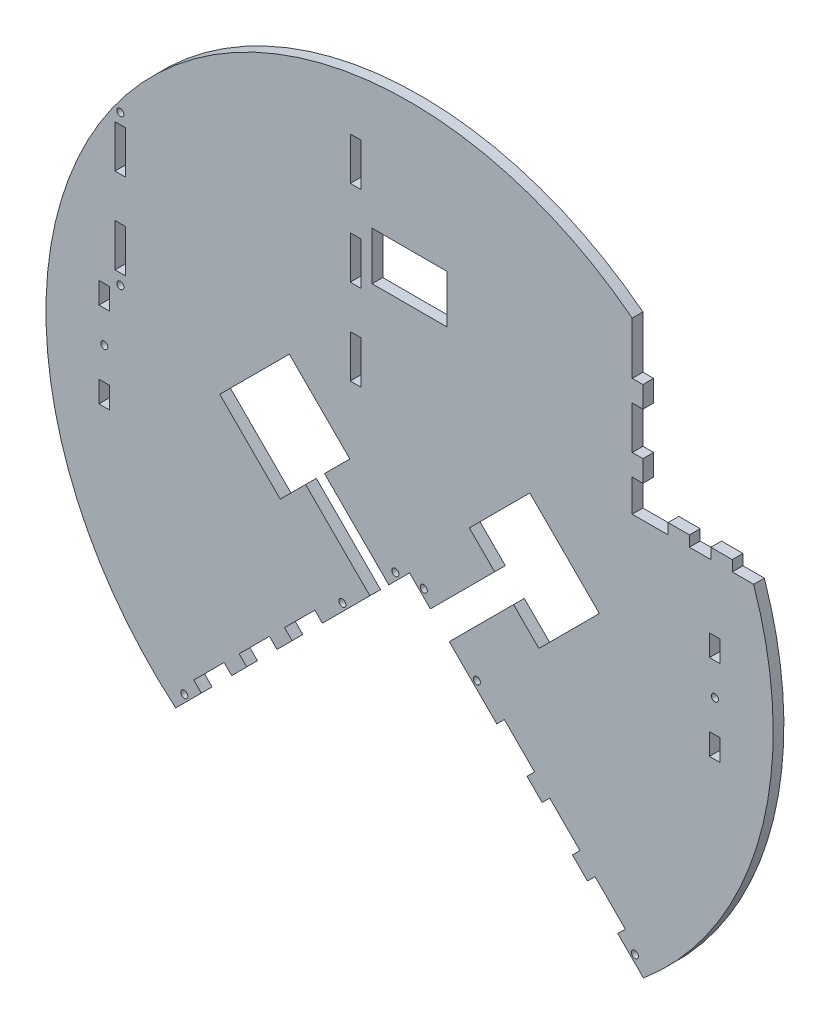
SolidWorks part; units mm, degrees
ref_plane "Front Plane" through (0, 0, 0) normal (0, 0, 1) x (1, 0, 0)
ref_plane "Top Plane" through (0, 0, 0) normal (0, 1, 0) x (1, 0, 0)
ref_plane "Right Plane" through (0, 0, 0) normal (1, 0, 0) x (0, 0, -1)
sketch "Sketch1" plane through (0, 0, 0) normal (0, 0, 1) x (1, 0, 0)
  circle A0 centre (0, 0) radius 215.9
  arc A1 (209.8384, 50.8) -> (202.0059, 76.2) centre (0, 0) ccw construction
extrude "Boss-Extrude1" add sketch "Sketch1" along normal blind 6.35 contours A0
sketch "Sketch2" plane through (0, 0, 0) normal (0, 0, -1) x (-1, 0, 0)
  line L0 (0, -26.4411) -> (138.8703, -165.3114)
  line L2 (0, -26.4411) -> (-138.8703, -165.3114)
  line L3 (-139.4438, -165.8849) -> (0, -26.4411) construction
  line L4 (0, 0) -> (0, -240.5018) construction
  arc A4 (-138.8703, -165.3114) -> (138.8703, -165.3114) centre (0, 0) ccw
  circle A5 centre (0, 0) radius 215.9 construction
  dimension "D1" = 90
extrude "Cut-Extrude1" cut sketch "Sketch2" against normal through all
sketch "Sketch3" plane through (0, 0, 6.35) normal (0, 0, 1) x (1, 0, 0)
  line L0 (71.393, 50.3401) -> (112.7022, 9.0309)
  line L1 (71.393, 50.3401) -> (35.472, 14.4191)
  line L2 (112.7022, 9.0309) -> (76.7812, -26.8901)
  line L3 (35.472, 14.4191) -> (76.7812, -26.8901)
  line L4 (76.7812, -26.8901) -> (72.2911, -22.4) construction
  line L5 (97.2507, 34.8885) -> (46.1575, -16.2046) construction
  line L6 (50.5139, -0.6229) -> (61.7393, -11.8482)
  line L7 (50.5139, -0.6229) -> (12.3479, -38.7889)
  line L8 (61.7393, -11.8482) -> (23.5732, -50.0143)
  line L9 (12.3479, -38.7889) -> (23.5732, -50.0143)
  line L10 (88.68, 15.0926) -> (77.4547, 26.3179) construction
  line L11 (0, -26.4411) -> (138.8703, -165.3114) construction
  line M8 (0, -26.4411) -> (138.8703, -165.3114)
extrude "Cut-Extrude2" cut sketch "Sketch3" against normal through all contours L8 L6 L3 L7 M8 | L0 L5 L6 L3 L2 | L5 L0 L1 L3 region at (63.7598, 22.0523, 6.35) region at (84.4144, 1.3977, 6.35) region at (37.0436, -25.3186, 6.35)
mirror "Mirror1" about plane through (0, 0, 0) normal (1, 0, 0) of "Cut-Extrude2"
sketch "Sketch4" plane through (0, 0, 6.35) normal (0, 0, 1) x (1, 0, 0)
  line L0 (-178.0884, 19.05) -> (-178.0884, 31.75) construction
  line L1 (178.0884, -19.05) -> (184.4384, -19.05)
  line L2 (178.0884, -19.05) -> (178.0884, -31.75)
  line L3 (178.0884, -31.75) -> (184.4384, -31.75)
  line L4 (184.4384, -19.05) -> (184.4384, -31.75)
  line L5 (178.0884, 31.75) -> (184.4384, 31.75)
  line L6 (178.0884, 31.75) -> (178.0884, 19.05)
  line L7 (178.0884, 19.05) -> (184.4384, 19.05)
  line L8 (184.4384, 31.75) -> (184.4384, 19.05)
  line L9 (178.0884, -19.05) -> (184.4384, -19.05)
  line L10 (178.0884, -19.05) -> (178.0884, -31.75)
  line L11 (178.0884, -31.75) -> (184.4384, -31.75)
  line L12 (184.4384, -19.05) -> (184.4384, -31.75)
  line L13 (-184.4384, 31.75) -> (-178.0884, 31.75)
  line L14 (-184.4384, 31.75) -> (-184.4384, 19.05)
  line L15 (-184.4384, 19.05) -> (-178.0884, 19.05)
  line L16 (-178.0884, 31.75) -> (-178.0884, 19.05)
  line L18 (-184.4384, -19.05) -> (-178.0884, -19.05)
  line L19 (-184.4384, -19.05) -> (-184.4384, -31.75)
  line L20 (-184.4384, -31.75) -> (-178.0884, -31.75)
  line L21 (-178.0884, -19.05) -> (-178.0884, -31.75)
extrude "Cut-Extrude3" cut sketch "Sketch4" against normal through all contours L21 L18 L19 L20 | L8 L5 L6 L7 | L4 L1 L2 L3 | L14 L15 L16 L13 region at (181.2634, -25.4, 6.35) region at (181.2634, 25.4, 6.35) region at (-181.2634, -25.4, 6.35)
sketch "Sketch5" plane through (0, 0, 6.35) normal (0, 0, 1) x (1, 0, 0)
  line L0 (-128.1057, -145.5666) -> (-110.1452, -127.6061)
  line L1 (-110.1452, -127.6061) -> (-105.6551, -132.0962)
  line L2 (-138.8703, -165.3114) -> (-23.5732, -50.0143) construction
  line L3 (-105.6551, -132.0962) -> (-110.1452, -127.6061) construction
  line L4 (-105.6551, -132.0962) -> (-123.6156, -150.0567)
  line L5 (-128.1057, -145.5666) -> (-123.6156, -150.0567) construction
  line L6 (-123.6156, -150.0567) -> (-128.1057, -145.5666)
extrude "Cut-Extrude4" cut sketch "Sketch5" against normal blind 6.35
pattern_linear "LPattern1" count 3 spacing 38.1 along (0.7071, 0.7071, 0) of "Cut-Extrude4"
sketch "Sketch6" plane through (0, 0, 6.35) normal (0, 0, 1) x (1, 0, 0)
  line L0 (110.1452, -127.6061) -> (128.1057, -145.5666)
  line L1 (128.1057, -145.5666) -> (123.6156, -150.0567)
  line L2 (23.5732, -50.0143) -> (138.8703, -165.3114) construction
  line L3 (123.6156, -150.0567) -> (128.1057, -145.5666) construction
  line L4 (123.6156, -150.0567) -> (105.6551, -132.0962)
  line L5 (110.1452, -127.6061) -> (105.6551, -132.0962) construction
  line L6 (105.6551, -132.0962) -> (110.1452, -127.6061)
extrude "Cut-Extrude5" cut sketch "Sketch6" against normal blind 6.35
pattern_linear "LPattern2" count 3 spacing 38.1 along (-0.7071, 0.7071, 0) of "Cut-Extrude5"
sketch "Sketch7" plane through (0, 0, 6.35) normal (0, 0, 1) x (1, 0, 0)
  line L0 (204.2885, 69.85) -> (132.2121, 69.85)
  line L1 (132.2121, 69.85) -> (132.2121, 170.6832)
  line L2 (221.1121, 69.85) -> (132.2121, 69.85) construction
  line L3 (132.2121, 76.2) -> (132.2121, 152.4) construction
  arc A0 (138.8703, -165.3114) -> (-138.8703, -165.3114) centre (0, 0) ccw construction
  arc A1 (204.2885, 69.85) -> (132.2121, 170.6832) centre (0, 0) ccw
extrude "Cut-Extrude6" cut sketch "Sketch7" against normal up to surface (6.35 mm away) up to face at (181.2634, -25.4, 0)
sketch "Sketch8" plane through (0, 0, 0) normal (0, 0, -1) x (-1, 0, 0)
  line L0 (174.9134, 41.9385) -> (174.9134, 67.3385) construction
  line L1 (28.8634, 181.6385) -> (35.2134, 181.6385)
  line L2 (28.8634, 181.6385) -> (28.8634, 156.2385)
  line L3 (28.8634, 156.2385) -> (35.2134, 156.2385)
  line L4 (35.2134, 181.6385) -> (35.2134, 156.2385)
  line L5 (28.8634, 130.8385) -> (35.2134, 130.8385)
  line L6 (28.8634, 130.8385) -> (28.8634, 105.4385)
  line L7 (28.8634, 105.4385) -> (35.2134, 105.4385)
  line L8 (35.2134, 130.8385) -> (35.2134, 105.4385)
  line L9 (28.8634, 80.0385) -> (35.2134, 80.0385)
  line L10 (28.8634, 80.0385) -> (28.8634, 54.6385)
  line L11 (28.8634, 54.6385) -> (35.2134, 54.6385)
  line L12 (35.2134, 80.0385) -> (35.2134, 54.6385)
  line L13 (168.5634, 118.1385) -> (174.9134, 118.1385)
  line L14 (168.5634, 118.1385) -> (168.5634, 92.7385)
  line L15 (168.5634, 92.7385) -> (174.9134, 92.7385)
  line L16 (174.9134, 118.1385) -> (174.9134, 92.7385)
  line L17 (168.5634, 67.3385) -> (174.9134, 67.3385)
  line L18 (168.5634, 67.3385) -> (168.5634, 41.9385)
  line L19 (168.5634, 41.9385) -> (174.9134, 41.9385)
  line L20 (174.9134, 67.3385) -> (174.9134, 41.9385)
extrude "Cut-Extrude7" cut sketch "Sketch8" against normal through all
sketch "Sketch9" plane through (132.2121, 0, 0) normal (1, 0, 0) x (0, 0, -1)
  line L0 (-6.35, 170.6832) -> (-6.35, 69.85) construction
  line L1 (-6.35, 88.9) -> (0, 88.9)
  line L2 (-6.35, 88.9) -> (-6.35, 101.6)
  line L3 (-6.35, 101.6) -> (0, 101.6)
  line L4 (0, 88.9) -> (0, 101.6)
  line L5 (0, 69.85) -> (0, 170.6832) construction
  line L6 (0, 69.85) -> (-6.35, 69.85) construction
  dimension "D1" = 12.7
  dimension "D2" = 19.05
extrude "Boss-Extrude2" add sketch "Sketch9" along normal blind 6.35
pattern_linear "LPattern3" count 2 spacing 38.1 along (0, 1, 0) of "Boss-Extrude2"
sketch "Sketch10" plane through (0, 69.85, 0) normal (0, 1, 0) x (1, 0, 0)
  line L0 (132.2121, -6.35) -> (204.2885, -6.35) construction
  line L1 (191.5885, -6.35) -> (178.8885, -6.35)
  line L2 (191.5885, -6.35) -> (191.5885, 0)
  line L3 (191.5885, 0) -> (178.8885, 0)
  line L4 (178.8885, -6.35) -> (178.8885, 0)
  line L5 (204.2885, 0) -> (132.2121, 0) construction
  dimension "D1" = 12.7
  dimension "D2" = 12.7
extrude "Boss-Extrude3" add sketch "Sketch10" along normal blind 6.35
pattern_linear "LPattern4" count 2 spacing 25.4 along (-1, 0, 0) of "Boss-Extrude3"
sketch "Sketch11" plane through (0, 0, 0) normal (0, 0, -1) x (-1, 0, 0)
  line L0 (184.4384, 2.1209) -> (178.0884, -2.1209) construction
  line L1 (184.4384, -2.1209) -> (178.0884, 2.1209) construction
  circle A0 centre (181.2634, 0) radius 2.0955
  dimension "D1" = 4.191
extrude "Wheel Hole" cut sketch "Sketch11" against normal through all
mirror "Mirror2" about plane through (0, 0, 0) normal (1, 0, 0) of "Wheel Hole"
sketch "Sketch12" plane through (0, 0, 6.35) normal (0, 0, 1) x (1, 0, 0)
  line L0 (0, 0) -> (0, 252.4228) construction
  line L1 (22.225, 111.125) -> (-22.225, 111.125)
  line L2 (22.225, 111.125) -> (22.225, 139.7)
  line L3 (22.225, 139.7) -> (-22.225, 139.7)
  line L4 (-22.225, 111.125) -> (-22.225, 139.7)
  arc A0 (132.2121, 170.6832) -> (-138.8703, -165.3114) centre (0, 0) ccw construction
  dimension "D3" = 139.7
  dimension "D1" = 28.575
  dimension "D2" = 44.45
extrude "Battery hole" cut sketch "Sketch12" against normal through all
sketch "Sketch13" plane through (0, 0, 0) normal (0, 0, -1) x (-1, 0, 0)
  line L0 (137.5285, -154.9894) -> (130.021, -156.4621) construction
  line L1 (134.5112, -151.972) -> (130.021, -156.4621) construction
  line L2 (138.8703, -165.3114) -> (123.6156, -150.0567) construction
  line L3 (134.5112, -151.972) -> (133.0384, -159.4795) construction
  line L4 (137.5285, -154.9894) -> (133.0384, -159.4795) construction
  line L5 (36.1647, -62.6058) -> (43.6722, -61.133) construction
  line L6 (51.7736, -78.2147) -> (23.5732, -50.0143) construction
  line L7 (40.6548, -58.1157) -> (36.1647, -62.6058) construction
  line L8 (39.1821, -65.6231) -> (40.6548, -58.1157) construction
  line L9 (43.6722, -61.133) -> (39.1821, -65.6231) construction
  line L10 (4.6652, -31.1063) -> (12.1727, -29.6336) construction
  line L11 (12.3479, -38.7889) -> (0, -26.4411) construction
  line L12 (9.1554, -26.6162) -> (4.6652, -31.1063) construction
  line L13 (7.6826, -34.1237) -> (9.1554, -26.6162) construction
  line L14 (12.1727, -29.6336) -> (7.6826, -34.1237) construction
  circle A0 centre (133.7748, -155.7257) radius 2.0955
  circle A1 centre (39.9184, -61.8694) radius 2.0955
  circle A2 centre (8.419, -30.37) radius 2.0955
  dimension "D1" = 4.191
extrude "Cut-Extrude10" cut sketch "Sketch13" against normal through all
mirror "Mirror3" about plane through (0, 0, 0) normal (1, 0, 0) of "Cut-Extrude10"
sketch "Sketch14" plane through (0, 0, 6.35) normal (0, 0, 1) x (1, 0, 0)
  line L0 (-174.9134, 126.6221) -> (-168.5634, 122.3549) construction
  line L1 (-168.5634, 126.6221) -> (-174.9134, 122.3549) construction
  line L2 (-174.9134, 37.7221) -> (-168.5634, 33.4549) construction
  line L3 (-174.9134, 33.4549) -> (-168.5634, 37.7221) construction
  circle A0 centre (-171.7384, 124.4885) radius 2.0955
  circle A1 centre (-171.7384, 35.5885) radius 2.0955
  dimension "D1" = 4.191
extrude "Cut-Extrude11" cut sketch "Sketch14" against normal through all
